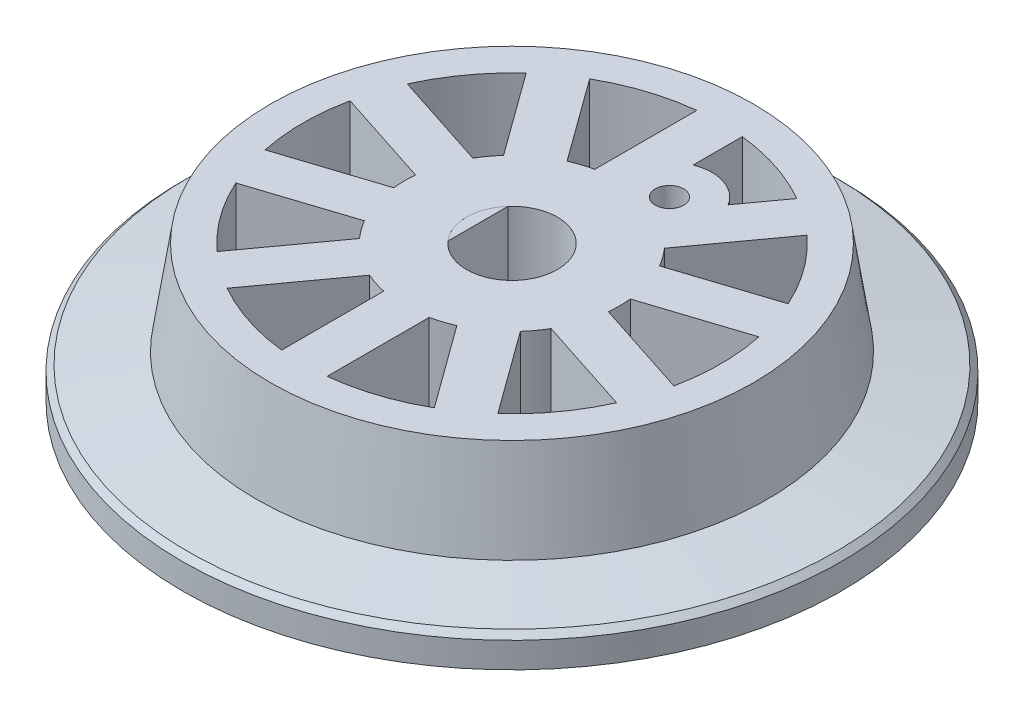
SolidWorks part; units mm, degrees
other "标注1"
sketch "草图3" plane through (-22.25, 4, -10) normal (-0.231, 0.6469, -0.7268) x (-0.9696, -0.2151, 0.1167)
ref_plane "前视基准面" through (0, 0, 0) normal (0, 0, 1) x (1, 0, 0)
ref_plane "上视基准面" through (0, 0, 0) normal (0, 1, 0) x (1, 0, 0)
ref_plane "右视基准面" through (0, 0, 0) normal (1, 0, 0) x (0, 0, -1)
other "Configuration Table"
sketch "草图4" plane through (0, 0, 0) normal (0, 1, 0) x (1, 0, 0)
  line L0 (-1.2, 1.0583) -> (-1.2, -1.0583)
  circle A0 centre (0, 0) radius 11.6
  circle A1 centre (0, 0) radius 1.6
  circle A2 centre (0, 0) radius 9
  dimension "D1" = 23.2
  dimension "D2" = 3.2
  dimension "D3" = 18
  dimension "D4" = 1.2
extrude "凸台-拉伸1" add sketch "草图4" along normal blind 1.1 contours A0 | A1
extrude "凸台-拉伸2" add sketch "草图4<3>" along normal blind 3.3 from offset 1.5 contours A2 | A1
sketch "草图4<3>" plane through (0, 0, 0) normal (0, 1, 0) x (1, 0, 0) same geometry as "草图4"
chamfer "倒角1" distance 0.2 angle 45 1 edges at (0, 1.1, 11.6)
loft "放样1" add section edge at (0, 1.5, 9) section edge at (0, 1.1, 11.4) connector at (0.6328, 1.5, 8.9777) connector at (2.6543, 1.1, 11.0867)
extrude "切除-拉伸2" cut sketch "草图4<4>" along normal through all contours A1
sketch "草图4<4>" plane through (0, 0, 0) normal (0, 1, 0) x (1, 0, 0) same geometry as "草图4"
chamfer "倒角2" distance 3.3 distance2 0.5 1 edges at (0, 4.8, 9) first distance on face at (0, 4.8, 9)
sketch "草图5" plane through (0, 4.8, 0) normal (0, 1, 0) x (1, 0, 0)
  line L0 (-0.8, 3.7148) -> (-0.8, 7.3063)
  line L1 (0, 3.8) -> (0, 7.35) construction
  line L2 (0.8, 7.3063) -> (0.8, 3.7148)
  circle A0 centre (0, 0) radius 3.8
  circle A1 centre (0, 0) radius 7.35
  dimension "D1" = 7.6
  dimension "D2" = 14.7
  dimension "D3" = 0.8
  dimension "D4" = 0.8
extrude "切除-拉伸4" cut sketch "草图5" against normal through all contours L0 A1 L2 A0 | A0 L1 A1 L0 | L1 A0 L2 A1 region at (-2.5179, 4.8, 3.1178) region at (-0.4008, 4.8, -5.5535) region at (0.4008, 4.8, -5.5535)
extrude "凸台-拉伸3" add sketch "草图5<4>" against normal up to surface (4.8 mm away) contours L1 A0 L2 A1 | A0 L1 A1 L0 region at (-0.4008, 4.8, -5.5535) region at (0.4008, 4.8, -5.5535) up to face at (0, 0, 7.35)
sketch "草图5<4>" plane through (0, 4.8, 0) normal (0, 1, 0) x (1, 0, 0) same geometry as "草图5"
pattern_circular "阵列(圆周)2" count 10 over 360 about axis through (0, 1.1, 0) along (0, -1, 0) of "凸台-拉伸3" reverse direction yes
sketch "草图6" plane through (0, 4.8, 0) normal (0, 1, 0) x (1, 0, 0)
  line L0 (0.8, 3.7148) -> (1.5363, 3.4756) construction
  line L1 (1.3597, 4.1846) -> (1.1682, 3.5952) construction
  circle A0 centre (1.3597, 4.1846) radius 0.5
  circle A1 centre (1.3597, 4.1846) radius 1.5
  dimension "D2" = 1
  dimension "D3" = 1
  dimension "D1" = 4.4
extrude "凸台-拉伸4" add sketch "草图6" against normal through all contours A1
extrude "切除-拉伸5" cut sketch "草图6<3>" against normal through all contours A0
sketch "草图6<3>" plane through (0, 4.8, 0) normal (0, 1, 0) x (1, 0, 0) same geometry as "草图6"
extrude "凸台-拉伸5" add sketch "草图4<6>" along normal up to surface (4.8 mm away) separate body contours L0 A1 region at (-1.3618, 0, 0) up to face at (1.3597, 4.8, -3.6846)
sketch "草图4<6>" plane through (0, 0, 0) normal (0, 1, 0) x (1, 0, 0) same geometry as "草图4"
